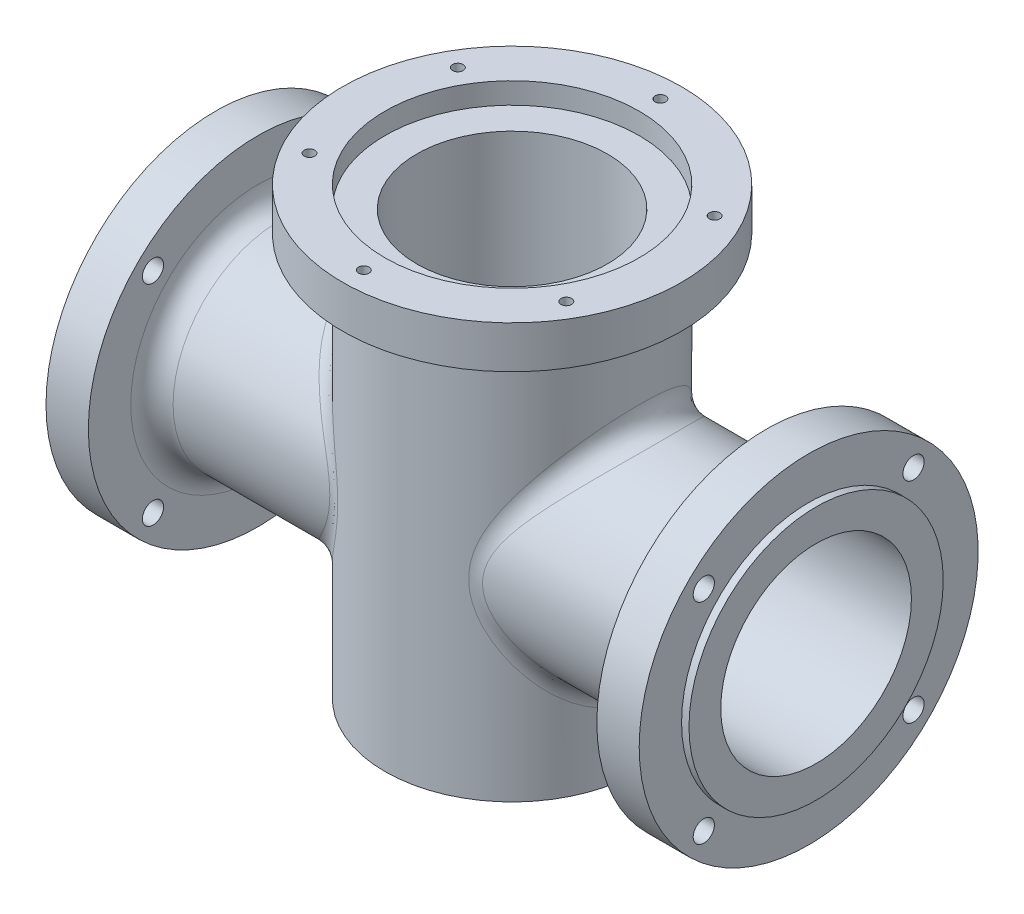
SolidWorks part; units mm, degrees
material "Ferro fundido cinza"
ref_plane "Plano frontal" through (0, 0, 0) normal (0, 0, 1) x (1, 0, 0)
ref_plane "Plano superior" through (0, 0, 0) normal (0, 1, 0) x (1, 0, 0)
ref_plane "Plano direito" through (0, 0, 0) normal (1, 0, 0) x (0, 0, -1)
sketch "Esboço1" plane through (0, 0, 0) normal (1, 0, 0) x (0, 0, -1)
  line L0 (0, 0) -> (0, 533.4) construction
  line L1 (-152.4, 533.4) -> (-203.2, 533.4)
  line L2 (-203.2, 533.4) -> (-203.2, 482.6)
  line L3 (-203.2, 482.6) -> (-177.8, 482.6)
  line L4 (-152.4, 457.2) -> (-152.4, 0)
  line L5 (-152.4, 0) -> (0, 0)
  line L6 (-152.4, 533.4) -> (-152.4, 508)
  line L7 (-152.4, 508) -> (-114.3, 508)
  line L8 (-114.3, 508) -> (-114.3, 25.4)
  line L9 (-114.3, 25.4) -> (0, 25.4)
  line L10 (-114.3, 508) -> (0, 508) construction
  line L11 (-152.4, 533.4) -> (0, 533.4) construction
  line L12 (0, 0) -> (0, 25.4)
  arc A0 (-177.8, 482.6) -> (-152.4, 457.2) centre (-177.8, 457.2) cw
  dimension "D9" = 25.4
  dimension "D1" = 25.4
  dimension "D2" = 482.6
  dimension "D3" = 25.4
  dimension "D4" = 406.4
  dimension "D5" = 304.8
  dimension "D6" = 304.8
  dimension "D7" = 50.8
  dimension "D8" = 228.6
revolve "Revolução1" add sketch "Esboço1" angle 360 about L0
sketch "Esboço2" plane through (0, 0, 0) normal (0, 0, 1) x (1, 0, 0)
  line L0 (-364.49, 228.6) -> (364.49, 228.6) construction
  line L1 (364.49, 228.6) -> (364.49, 381)
  line L2 (364.49, 381) -> (355.6, 381)
  line L3 (355.6, 381) -> (355.6, 431.8)
  line L4 (355.6, 431.8) -> (304.8, 431.8)
  line L5 (304.8, 431.8) -> (304.8, 381)
  line L6 (279.4, 355.6) -> (-279.4, 355.6)
  line L7 (-304.8, 381) -> (-304.8, 431.8)
  line L8 (-304.8, 431.8) -> (-355.6, 431.8)
  line L9 (-355.6, 431.8) -> (-355.6, 381)
  line L10 (-355.6, 381) -> (-364.49, 381)
  line L11 (-364.49, 381) -> (-364.49, 228.6)
  line L12 (0, 355.6) -> (0, 0) construction
  line L13 (-152.4, 0) -> (152.4, 0) construction
  line L14 (-364.49, 228.6) -> (364.49, 228.6)
  arc A0 (304.8, 381) -> (279.4, 355.6) centre (279.4, 381) cw
  arc A1 (-279.4, 355.6) -> (-304.8, 381) centre (-279.4, 381) cw
  dimension "D11" = 25.4
  dimension "D1" = 8.89
  dimension "D2" = 8.89
  dimension "D3" = 50.8
  dimension "D4" = 50.8
  dimension "D5" = 711.2
  dimension "D6" = 228.6
  dimension "D7" = 304.8
  dimension "D8" = 254
  dimension "D9" = 406.4
  dimension "D10" = 406.4
revolve "Revolução2" add sketch "Esboço2" angle 360 about L14
sketch "Esboço3" plane through (0, 508, 0) normal (0, 1, 0) x (1, 0, 0)
  circle A0 centre (0, 0) radius 114.3 construction
  circle A1 centre (0, 0) radius 114.3
extrude "Corte-extrusão1" cut sketch "Esboço3" against normal blind 482.6
sketch "Esboço4" plane through (364.49, 0, 0) normal (1, 0, 0) x (0, 0, -1)
  circle A0 centre (0, 228.6) radius 114.3
  dimension "D1" = 228.6
extrude "Corte-extrusão2" cut sketch "Esboço4" against normal through all
fillet "Filete1" radius 25.4 2 edges at (-86.513, 208.9089, -125.4642) (86.513, 248.2911, -125.4642)
sketch "Esboço5" plane through (0, 533.4, 0) normal (0, 1, 0) x (1, 0, 0)
  line L0 (0, 0) -> (0, 177.8) construction
  line L1 (0, 0) -> (177.8, 0) construction
  circle A0 centre (0, 0) radius 177.8 construction
  circle A1 centre (0, 177.8) radius 6.35
  dimension "D1" = 355.6
  dimension "D2" = 12.7
extrude "Corte-extrusão3" cut sketch "Esboço5" against normal blind 62
pattern_circular "PadrãoCircular1" count 6 over 360 about axis through (0, 533.4, 0) along (0, -1, 0) of "Corte-extrusão3"
sketch "Esboço6" plane through (355.6, 0, 0) normal (1, 0, 0) x (0, 0, -1)
  line L0 (0, 228.6) -> (177.8, 228.6) construction
  line L1 (0, 228.6) -> (125.7236, 354.3236) construction
  circle A0 centre (0, 228.6) radius 177.8 construction
  circle A1 centre (125.7236, 354.3236) radius 12.7
  circle A2 centre (125.7236, 102.8764) radius 12.7
  circle A3 centre (-125.7236, 102.8764) radius 12.7
  circle A4 centre (-125.7236, 354.3236) radius 12.7
  point P15 (0, 228.6)
  dimension "D1" = 355.6
  dimension "D3" = 25.4
  dimension "D2" = 45
  dimension "D4" = 4
extrude "Corte-extrusão4" cut sketch "Esboço6" against normal blind 60
mirror "Espelhar1" about plane through (0, 0, 0) normal (1, 0, 0) of "Corte-extrusão4"
